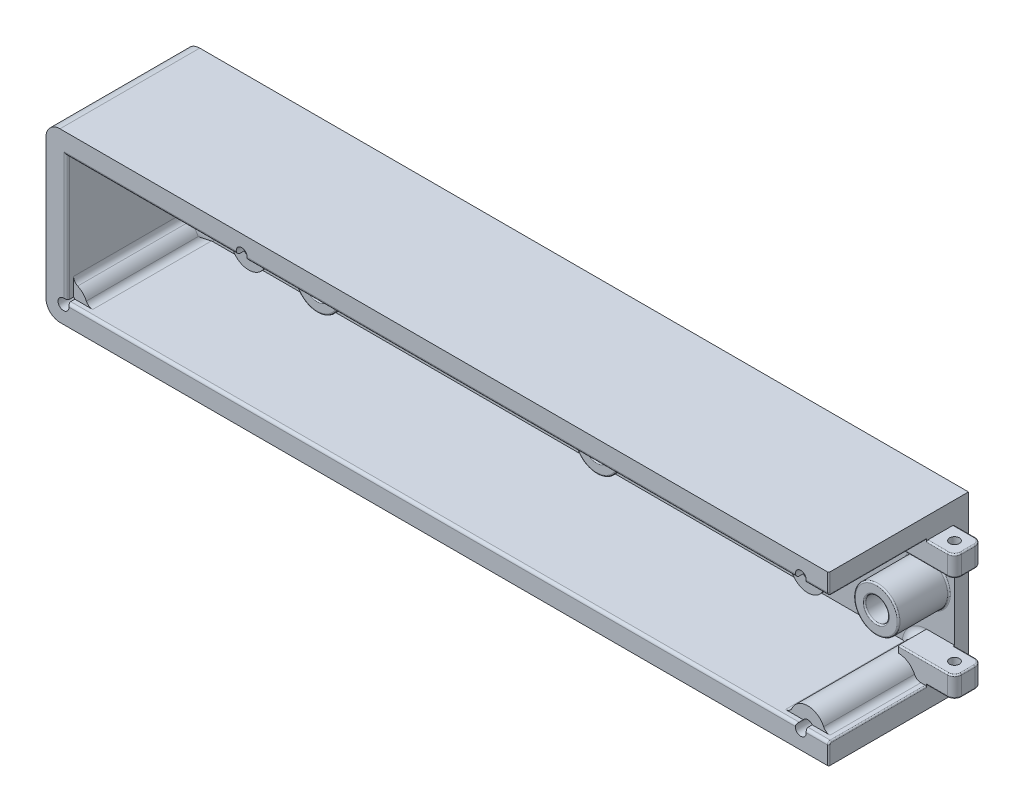
SolidWorks part; units mm, degrees
ref_plane "Front Plane" through (0, 0, 0) normal (0, 0, 1) x (1, 0, 0)
ref_plane "Top Plane" through (0, 0, 0) normal (0, 1, 0) x (1, 0, 0)
ref_plane "Right Plane" through (0, 0, 0) normal (1, 0, 0) x (0, 0, -1)
sketch "Sketch1" plane through (0, 0, 0) normal (0, 0, 1) x (1, 0, 0)
  line L0 (-50, 0) -> (0, 0) construction
  line L1 (-420, -70) -> (420, -70)
  line L2 (-420, -70) -> (-420, 70)
  line L3 (-420, 70) -> (420, 70)
  line L4 (420, -70) -> (420, 70)
  line L5 (-420, -70) -> (420, 70) construction
  line L6 (-420, 70) -> (420, -70) construction
  line L7 (0, 0) -> (50, 0) construction
  line L8 (250, 0) -> (350, 0) construction
  line L9 (333.7, -57.5) -> (333.7, 17.5)
  line L14 (334, -40) -> (350, 0) construction
  line L15 (334, 40) -> (334.4358, 38.9104) construction
  line L16 (336.5, 20.3) -> (363.5, 20.3)
  line L17 (366.3, -57.5) -> (366.3, 17.5)
  line L18 (336.5, -60.3) -> (363.5, -60.3)
  line L21 (365.5642, -38.9104) -> (366, -40) construction
  line L22 (365.5642, 38.9104) -> (366, 40) construction
  circle A0 centre (-350, 0) radius 4.15
  circle A1 centre (-250, 0) radius 4.15
  circle A2 centre (-150, 0) radius 4.15
  circle A3 centre (-50, 0) radius 4.15
  circle A4 centre (50, 0) radius 4.15
  circle A5 centre (150, 0) radius 4.15
  circle A6 centre (250, 0) radius 4.15
  circle A8 centre (350, 0) radius 4.15 [skipped]
  arc A13 (333.7, 17.5) -> (336.5, 20.3) centre (336.5, 17.5) cw
  arc A14 (363.5, 20.3) -> (366.3, 17.5) centre (363.5, 17.5) cw
  arc A15 (363.5, -60.3) -> (366.3, -57.5) centre (363.5, -57.5) ccw
  arc A16 (336.5, -60.3) -> (333.7, -57.5) centre (336.5, -57.5) cw
  point P0 (0, 0)
  dimension "D3" = 8.3
  dimension "D5" = 80
  dimension "D1" = 840
  dimension "D2" = 140
  dimension "D6" = 32
  dimension "D4" = 8
extrude "Boss-Extrude1" add sketch "Sketch1" along normal blind 5
sketch "Sketch2" plane through (0, 0, 5) normal (0, 0, 1) x (1, 0, 0)
  circle A0 centre (-350, 0) radius 8
  circle A1 centre (-350, 0) radius 4.15
extrude "Boss-Extrude3" add sketch "Sketch2" along normal blind 18
pattern_linear "LPattern1" count 7 spacing 100 along (1, 0, 0) of "Boss-Extrude3"
sketch "Sketch4" plane through (0, 0, 0) normal (0, 0, -1) x (-1, 0, 0)
  line L1 (-372.738, 24.1165) -> (-327.1271, 24.1165)
  line L2 (-372.738, 24.1165) -> (-372.738, -63.8212)
  line L3 (-372.738, -63.8212) -> (-327.1271, -63.8212)
  line L4 (-327.1271, 24.1165) -> (-327.1271, -63.8212)
extrude "Boss-Extrude4" add sketch "Sketch4" against normal blind 1
sketch "Sketch5" plane through (0, 70, 0) normal (0, 1, 0) x (1, 0, 0)
  line L4 (420, 0) -> (-420, 0)
  line L5 (-420, 0) -> (-420, -5)
  line L6 (-420, -5) -> (420, -5)
  line L7 (420, -5) -> (420, 0)
  line L8 (420, 0) -> (-420, 0)
  line L9 (-420, 0) -> (-420, -5)
  line L10 (-420, -5) -> (420, -5)
  line L11 (420, -5) -> (420, 0)
  dimension "D1" = 0
extrude "Cut-Extrude1" cut sketch "Sketch5" against normal blind 40
sketch "Sketch6" plane through (0, 0, 5) normal (0, 0, 1) x (1, 0, 0)
  line L0 (420, -70) -> (420, 30) construction
  line L1 (-420, -70) -> (300, -70)
  line L2 (-420, -70) -> (-420, -30)
  line L3 (-420, -30) -> (300, -30)
  line L4 (300, -70) -> (300, -30)
  dimension "D1" = 40
  dimension "D2" = 120
extrude "Cut-Extrude2" cut sketch "Sketch6" against normal through all
fillet "Fillet1" radius 5 4 edges at (300, -70, 2.5) (300, -30, 2.5) (-420, -30, 2.5) (-420, 30, 2.5)
fillet "Fillet2" radius 0.5 29 edges at (365.4799, -59.4799, 5) (350, -60.3, 5) (334.5201, -59.4799, 5) (333.7, -20, 5) (334.5201, 19.4799, 5) (350, 20.3, 5) (365.4799, 19.4799, 5) (-145.85, 0, 23) (-142, 0, 23) (-245.85, 0, 23) (-242, 0, 23) (366.3, -20, 5) (254.15, 0, 23) (258, 0, 23) (154.15, 0, 23) (158, 0, 23) (54.15, 0, 23) (58, 0, 23) (-45.85, 0, 23) (-42, 0, 23) (242, 0, 5) (142, 0, 5) (42, 0, 5) (-58, 0, 5) (-158, 0, 5) (-258, 0, 5) (-345.85, 0, 23) (-342, 0, 23) (-358, 0, 5)
fillet "Fillet3" radius 1 8 edges at (334.5201, 19.4799, 1) (333.7, -20, 1) (334.5201, -59.4799, 1) (350, -60.3, 1) (365.4799, -59.4799, 1) (366.3, -20, 1) (365.4799, 19.4799, 1) (350, 20.3, 1)
sketch "Sketch8" plane through (0, 0, 5) normal (0, 0, 1) x (1, 0, 0)
  line L0 (412.625, -62.625) -> (412.625, 22.625)
  line L1 (412.625, 22.625) -> (-412.625, 22.625)
  line L2 (-412.625, 22.625) -> (-412.625, -22.625)
  line L3 (-412.625, -22.625) -> (295, -22.625)
  line L4 (307.375, -35) -> (307.375, -62.625)
  line L5 (307.375, -62.625) -> (412.625, -62.625)
  line L6 (300, -35) -> (300, -65)
  line L7 (305, -70) -> (420, -70)
  line L8 (420, -70) -> (420, 30)
  line L9 (420, 30) -> (-415, 30)
  line L10 (-420, 25) -> (-420, -25)
  line L11 (-415, -30) -> (295, -30)
  line L12 (300, -35) -> (300, -65)
  line L13 (305, -70) -> (420, -70)
  line L14 (420, -70) -> (420, 30)
  line L15 (420, 30) -> (-415, 30)
  line L16 (-420, 25) -> (-420, -25)
  line L17 (-415, -30) -> (295, -30)
  arc A0 (-412.625, 22.625) -> (-412.625, 22.625) centre (-412.625, 22.625) ccw
  arc A1 (-412.625, -22.625) -> (-412.625, -22.625) centre (-412.625, -22.625) ccw
  arc A2 (307.375, -35) -> (295, -22.625) centre (295, -35) ccw
  arc A3 (307.375, -62.625) -> (307.375, -62.625) centre (307.375, -62.625) ccw
  arc A4 (300, -65) -> (305, -70) centre (305, -65) ccw
  arc A5 (-415, 30) -> (-420, 25) centre (-415, 25) ccw
  arc A6 (-420, -25) -> (-415, -30) centre (-415, -25) ccw
  arc A7 (300, -35) -> (295, -30) centre (295, -35) ccw
  arc A8 (300, -65) -> (305, -70) centre (305, -65) ccw
  arc A9 (-415, 30) -> (-420, 25) centre (-415, 25) ccw
  arc A10 (-420, -25) -> (-415, -30) centre (-415, -25) ccw
  arc A11 (300, -35) -> (295, -30) centre (295, -35) ccw
  dimension "D1" = 0
  dimension "D2" = 7.375
extrude "Boss-Extrude5" add sketch "Sketch8" along normal blind 45
ref_plane "Plane1" through (-140, 0, 0) normal (-1, 0, 0) x (0, 0, 1)
ref_plane "Plane2" through (140, 0, 0) normal (-1, 0, 0) x (0, 0, 1)
fillet "Fillet4" radius 1 3 edges at (307.375, -48.8125, 50) (303.7504, -26.2496, 50) (-58.8125, -22.625, 50)
sketch "Sketch10" plane through (0, 0, 50) normal (0, 0, 1) x (1, 0, 0)
  line L0 (412.625, -62.625) -> (412.625, 22.625) construction
  line L1 (412.625, 22.625) -> (420, 22.625)
  line L2 (412.625, 22.625) -> (412.625, -62.625)
  line L3 (412.625, -62.625) -> (420, -62.625)
  line L4 (420, 22.625) -> (420, -62.625)
  line L5 (412.625, -62.625) -> (412.625, 22.625) construction
  line L6 (420, -70) -> (420, 30) construction
extrude "Cut-Extrude3" cut sketch "Sketch10" against normal up to surface (45 mm away) up to face at (130.3304, -22.5267, 5)
fillet "Fillet5" radius 1 3 edges at (-412.625, -0.5, 50) (3.6875, 22.625, 50) (363.1875, -62.625, 50)
sketch "Sketch11" plane through (0, 0, 0) normal (0, 0, -1) x (-1, 0, 0)
  circle A0 centre (-250, 0) radius 4.15
  circle A1 centre (-150, 0) radius 4.15
  circle A2 centre (-50, 0) radius 4.15
  circle A3 centre (50, 0) radius 4.15
  circle A4 centre (150, 0) radius 4.15
  circle A5 centre (250, 0) radius 4.15
  circle A6 centre (350, 0) radius 4.15
  dimension "D1" = 7
extrude "Boss-Extrude6" add sketch "Sketch11" against normal blind 5
mirror "Mirror1" about plane through (420, -70, 5) normal (-1, 0, 0) of bodies 110
delete or keep bodies "Body-Delete/Keep 2" type delete bodies bodies 110
sketch "Sketch12" plane through (420, 0, 0) normal (-1, 0, 0) x (0, 0, 1)
  line L8 (50, 23.625) -> (50, 30)
  line L9 (50, 30) -> (0, 30)
  line L10 (0, 30) -> (0, -70)
  line L11 (0, -70) -> (50, -70)
  line L12 (50, -70) -> (50, -63.625)
  line L13 (49, -62.625) -> (5, -62.625)
  line L14 (5, -62.625) -> (5, 22.625)
  line L15 (5, 22.625) -> (49, 22.625)
  line L16 (50, 23.625) -> (50, 30)
  line L17 (50, 30) -> (0, 30)
  line L18 (0, 30) -> (0, -70)
  line L19 (0, -70) -> (50, -70)
  line L20 (50, -70) -> (50, -63.625)
  line L21 (49, -62.625) -> (5, -62.625)
  line L22 (5, -62.625) -> (5, 22.625)
  line L23 (5, 22.625) -> (49, 22.625)
  arc A2 (50, -63.625) -> (49, -62.625) centre (49, -63.625) ccw
  arc A3 (49, 22.625) -> (50, 23.625) centre (49, 23.625) ccw
  arc A4 (50, -63.625) -> (49, -62.625) centre (49, -63.625) ccw
  arc A5 (49, 22.625) -> (50, 23.625) centre (49, 23.625) ccw
  dimension "D1" = 0
extrude "Cut-Extrude4" cut sketch "Sketch12" against normal blind 20
sketch "Sketch13" plane through (0, -70, 0) normal (0, -1, 0) x (1, 0, 0)
  line L0 (535, 50) -> (440, 50) construction
  line L1 (455, 35) -> (467, 35)
  line L2 (455, 35) -> (455, 23)
  line L3 (455, 23) -> (467, 23)
  line L4 (467, 35) -> (467, 23)
  line L5 (440, 0) -> (440, 50) construction
  point P6 (455, 29)
  dimension "D1" = 12
  dimension "D2" = 12
  dimension "D3" = 15
  dimension "D4" = 15
extrude "Cut-Extrude5" cut sketch "Sketch13" against normal blind 5
sketch "Sketch14" plane through (0, -70, 0) normal (0, -1, 0) x (1, 0, 0)
  line L0 (467, 35) -> (455, 35) construction
  line L1 (456.5, 37) -> (465.5, 37)
  line L2 (456.5, 37) -> (456.5, 21)
  line L3 (456.5, 21) -> (465.5, 21)
  line L4 (465.5, 37) -> (465.5, 21)
  line L5 (455, 35) -> (455, 23) construction
  point P4 (461, 35)
  point P5 (455, 29)
  point P8 (461, 37)
  point P11 (456.5, 29)
  dimension "D1" = 9
  dimension "D2" = 16
extrude "Cut-Extrude6" cut sketch "Sketch14" against normal up to next
sketch "Sketch20" plane through (0, 0, 50) normal (0, 0, 1) x (1, 0, 0)
  line L0 (440, 30) -> (1255, 30) construction
  line L1 (1255, -30) -> (545, -30) construction
  line L2 (540, -35) -> (540, -65) construction
  line L3 (535, -70) -> (440, -70) construction
  line L5 (440, 23.625) -> (440, 30) construction
  line L12 (1255, 30) -> (440, 30)
  line L13 (440, 30) -> (440, 23.625)
  line L14 (440, 23.625) -> (1253.625, 23.625)
  line L15 (1253.625, 23.625) -> (1253.625, -23.625)
  line L16 (1253.625, -23.625) -> (545, -23.625)
  line L17 (533.625, -35) -> (533.625, -63.625)
  line L18 (533.625, -63.625) -> (440, -63.625)
  line L19 (440, -63.625) -> (440, -70)
  line L20 (440, -70) -> (535, -70)
  line L21 (540, -65) -> (540, -35)
  line L22 (545, -30) -> (1255, -30)
  line L23 (1260, -25) -> (1260, 25)
  line L35 (1260, -25) -> (1260, 25)
  circle A0 centre (790, 23.75) radius 1.95
  circle A1 centre (790, -23.75) radius 1.95
  circle A4 centre (460, 23.75) radius 1.95
  arc A5 (545, -23.625) -> (533.625, -35) centre (545, -35) ccw
  arc A6 (535, -70) -> (540, -65) centre (535, -65) ccw
  arc A7 (545, -30) -> (540, -35) centre (545, -35) ccw
  arc A8 (1255, -30) -> (1260, -25) centre (1255, -25) ccw
  arc A9 (1260, 25) -> (1255, 30) centre (1255, 25) ccw
  arc A11 (535, -70) -> (540, -65) centre (535, -65) ccw
  arc A12 (545, -30) -> (540, -35) centre (545, -35) ccw
  arc A13 (1255, -30) -> (1260, -25) centre (1255, -25) ccw
  arc A14 (1260, 25) -> (1255, 30) centre (1255, 25) ccw
  circle A15 centre (533.75, -63.75) radius 1.95
  circle A16 centre (690, 23.75) radius 1.95
  circle A17 centre (890, -23.75) radius 1.95
  circle A18 centre (990, 23.75) radius 1.95
  circle A19 centre (690, -23.75) radius 1.95
  circle A20 centre (890, 23.75) radius 1.95
  circle A21 centre (990, -23.75) radius 1.95
  circle A22 centre (1190, 23.75) radius 1.95
  circle A23 centre (1253.75, -23.75) radius 1.95
  point P13 (890, 0)
  point P28 (790, 0)
  point P44 (690, 0)
  point P46 (689.7552, 26.25)
  point P49 (990, 0)
  point P63 (1190, 0)
  dimension "D3" = 20
  dimension "D4" = 3.9
  dimension "D5" = 6.25
  dimension "D2" = 6.25
  dimension "D6" = 6.25
  dimension "D7" = 6.25
  dimension "D8" = 6.25
  dimension "D9" = 6.25
  dimension "D10" = 6.25
  dimension "D11" = 6.25
  dimension "D1" = 0
extrude "Cut-Extrude8" cut sketch "Sketch20" against normal blind 26 contours A4 | A15 | A16 | A19 | A20 | A17 | A18 | A21 | A22 | A23 | A1 | A0
ref_plane "Plane5" through (700, 0, 0) normal (-1, 0, 0) x (0, 0, 1)
ref_plane "Plane6" through (980, 0, 0) normal (-1, 0, 0) x (0, 0, 1)
ref_plane "Plane7" through (0, 0, 47.5) normal (0, 0, 1) x (1, 0, 0)
sketch "Sketch22" plane through (0, 0, 47.5) normal (0, 0, 1) x (1, 0, 0)
  circle A0 centre (460, 23.75) radius 1.95
  circle A1 centre (460, 23.75) radius 6.25
  circle A2 centre (690, 23.75) radius 1.95
  circle A3 centre (690, 23.75) radius 6.25
  circle A4 centre (790, 23.75) radius 1.95
  circle A5 centre (790, 23.75) radius 6.25
  circle A6 centre (890, 23.75) radius 1.95
  circle A7 centre (890, 23.75) radius 6.25
  circle A8 centre (990, 23.75) radius 1.95
  circle A9 centre (990, 23.75) radius 6.25
  circle A10 centre (1190, 23.75) radius 1.95
  circle A11 centre (1190, 23.75) radius 6.25
  circle A12 centre (1253.75, -23.75) radius 1.95
  circle A13 centre (1253.75, -23.75) radius 6.25
  circle A14 centre (990, -23.75) radius 1.95
  circle A16 centre (990, -23.75) radius 6.25
  circle A17 centre (890, -23.75) radius 1.95
  circle A18 centre (890, -23.75) radius 6.25
  circle A19 centre (790, -23.75) radius 1.95
  circle A20 centre (790, -23.75) radius 6.25
  circle A21 centre (690, -23.75) radius 1.95
  circle A22 centre (690, -23.75) radius 6.25
  circle A23 centre (533.75, -63.75) radius 1.95
  circle A24 centre (533.75, -63.75) radius 6.25
extrude "Boss-Extrude8" add sketch "Sketch22" against normal up to surface (42.5 mm away) up to face at (1198.5, 0, 5)
sketch "Sketch23" plane through (0, 0, 5) normal (0, 0, 1) x (1, 0, 0)
  line L1 (461.5928, 22.625) -> (458.4072, 22.625)
  line L2 (461.5928, 22.625) -> (458.4072, 22.625)
  line L3 (691.5928, 22.625) -> (688.4072, 22.625)
  line L4 (691.5928, 22.625) -> (688.4072, 22.625)
  line L5 (791.5928, 22.625) -> (788.4072, 22.625)
  line L6 (791.5928, 22.625) -> (788.4072, 22.625)
  line L7 (891.5928, 22.625) -> (888.4072, 22.625)
  line L8 (891.5928, 22.625) -> (888.4072, 22.625)
  line L9 (991.5928, 22.625) -> (988.4072, 22.625)
  line L10 (991.5928, 22.625) -> (988.4072, 22.625)
  line L11 (1191.5928, 22.625) -> (1188.4072, 22.625)
  line L12 (1191.5928, 22.625) -> (1188.4072, 22.625)
  line L13 (988.4072, -22.625) -> (991.5928, -22.625)
  line L14 (1252.1572, -22.625) -> (1252.625, -22.625)
  line L15 (1252.625, -22.625) -> (1252.625, -22.1572)
  line L16 (1252.1572, -22.625) -> (1252.625, -22.625)
  line L17 (1252.625, -22.625) -> (1252.625, -22.1572)
  line L18 (988.4072, -22.625) -> (991.5928, -22.625)
  line L19 (888.4072, -22.625) -> (891.5928, -22.625)
  line L20 (888.4072, -22.625) -> (891.5928, -22.625)
  line L21 (788.4072, -22.625) -> (791.5928, -22.625)
  line L22 (788.4072, -22.625) -> (791.5928, -22.625)
  line L23 (688.4072, -22.625) -> (691.5928, -22.625)
  line L24 (688.4072, -22.625) -> (691.5928, -22.625)
  line L26 (532.1572, -62.625) -> (532.625, -62.625)
  line L27 (532.625, -62.625) -> (532.625, -62.1572)
  line L28 (532.1572, -62.625) -> (532.625, -62.625)
  line L29 (532.625, -62.625) -> (532.625, -62.1572)
  arc A1 (458.4072, 22.625) -> (461.5928, 22.625) centre (460, 23.75) ccw
  arc A2 (458.4072, 22.625) -> (461.5928, 22.625) centre (460, 23.75) ccw
  arc A3 (688.4072, 22.625) -> (691.5928, 22.625) centre (690, 23.75) ccw
  arc A4 (688.4072, 22.625) -> (691.5928, 22.625) centre (690, 23.75) ccw
  arc A5 (788.4072, 22.625) -> (791.5928, 22.625) centre (790, 23.75) ccw
  arc A6 (788.4072, 22.625) -> (791.5928, 22.625) centre (790, 23.75) ccw
  arc A7 (888.4072, 22.625) -> (891.5928, 22.625) centre (890, 23.75) ccw
  arc A8 (888.4072, 22.625) -> (891.5928, 22.625) centre (890, 23.75) ccw
  arc A9 (988.4072, 22.625) -> (991.5928, 22.625) centre (990, 23.75) ccw
  arc A10 (988.4072, 22.625) -> (991.5928, 22.625) centre (990, 23.75) ccw
  arc A11 (1188.4072, 22.625) -> (1191.5928, 22.625) centre (1190, 23.75) ccw
  arc A12 (1188.4072, 22.625) -> (1191.5928, 22.625) centre (1190, 23.75) ccw
  arc A13 (1252.625, -22.1572) -> (1252.1572, -22.625) centre (1253.75, -23.75) ccw
  arc A14 (1252.625, -22.1572) -> (1252.1572, -22.625) centre (1253.75, -23.75) ccw
  arc A15 (991.5928, -22.625) -> (988.4072, -22.625) centre (990, -23.75) ccw
  arc A16 (991.5928, -22.625) -> (988.4072, -22.625) centre (990, -23.75) ccw
  arc A17 (891.5928, -22.625) -> (888.4072, -22.625) centre (890, -23.75) ccw
  arc A18 (891.5928, -22.625) -> (888.4072, -22.625) centre (890, -23.75) ccw
  arc A19 (791.5928, -22.625) -> (788.4072, -22.625) centre (790, -23.75) ccw
  arc A20 (791.5928, -22.625) -> (788.4072, -22.625) centre (790, -23.75) ccw
  arc A21 (691.5928, -22.625) -> (688.4072, -22.625) centre (690, -23.75) ccw
  arc A22 (691.5928, -22.625) -> (688.4072, -22.625) centre (690, -23.75) ccw
  arc A23 (532.625, -62.1572) -> (532.1572, -62.625) centre (533.75, -63.75) ccw
  arc A24 (532.625, -62.1572) -> (532.1572, -62.625) centre (533.75, -63.75) ccw
  dimension "D1" = 0
  dimension "D2" = 0
  dimension "D3" = 0
  dimension "D4" = 0
  dimension "D5" = 0
  dimension "D6" = 0
  dimension "D7" = 0
  dimension "D8" = 0
  dimension "D9" = 0
  dimension "D10" = 0
  dimension "D11" = 0
  dimension "D12" = 0
extrude "Boss-Extrude9" add sketch "Sketch23" along normal up to surface (19 mm away) up to face at (460, 24.1625, 24)
fillet "Fillet6" radius 2.5 36 edges at (1252.625, -17.6021, 26.25) (1247.6021, -22.625, 26.25) (1249.3306, -19.3306, 5) (996.1479, -22.625, 26.25) (990, -17.5, 5) (983.8521, -22.625, 26.25) (890, -17.5, 5) (883.8521, -22.625, 26.25) (896.1479, -22.625, 26.25) (796.1479, -22.625, 26.25) (783.8521, -22.625, 26.25) (790, -17.5, 5) (696.1479, -22.625, 26.25) (690, -17.5, 5) (683.8521, -22.625, 26.25) (532.625, -57.6021, 26.25) (529.3306, -59.3306, 5) (527.6021, -62.625, 26.25) (453.8521, 22.625, 26.25) (466.1479, 22.625, 26.25) (683.8521, 22.625, 26.25) (696.1479, 22.625, 26.25) (783.8521, 22.625, 26.25) (796.1479, 22.625, 26.25) (896.1479, 22.625, 26.25) (883.8521, 22.625, 26.25) (983.8521, 22.625, 26.25) (996.1479, 22.625, 26.25) (1196.1479, 22.625, 26.25) (1183.8521, 22.625, 26.25) (1190, 17.5, 5) (990, 17.5, 5) (890, 17.5, 5) (790, 17.5, 5) (690, 17.5, 5) (460, 17.5, 5)
ref_plane "Plane8" through (980, 0, 0) normal (-1, 0, 0) x (0, 0, 1)
sketch "Sketch25" plane through (440, 0, 0) normal (-1, 0, 0) x (0, 0, 1)
  line L1 (-34.7781, 41.231) -> (83.3252, 41.231)
  line L2 (-34.7781, 41.231) -> (-34.7781, -92.647)
  line L3 (-34.7781, -92.647) -> (83.3252, -92.647)
  line L4 (83.3252, 41.231) -> (83.3252, -92.647)
extrude "Cut-Extrude10" cut sketch "Sketch25" against normal up to surface (540 mm away) up to plane "Plane8"
sketch "Sketch26" plane through (0, 0, 5) normal (0, 0, 1) x (1, 0, 0)
  line L0 (990, 15) -> (980, 15)
  line L1 (980, -22.625) -> (980, 22.625) construction
  line L2 (980, 15) -> (980, 22.625)
  line L3 (980, 22.625) -> (981.3226, 22.625) construction
  line L4 (980, 22.625) -> (988.4072, 22.625)
  line L5 (990, 21.8) -> (990, 15)
  circle A0 centre (990, 23.75) radius 1.95 construction
  arc A1 (988.4072, 22.625) -> (990, 21.8) centre (990, 23.75) ccw
  arc A2 (981.3226, 22.625) -> (998.6774, 22.625) centre (990, 23.75) ccw construction
  dimension "D1" = 0
extrude "Boss-Extrude10" add sketch "Sketch26" along normal blind 10
sketch "Sketch27" plane through (980, 0, 0) normal (-1, 0, 0) x (0, 0, 1)
  line L0 (5, 22.625) -> (5, -15.0726) construction
  line L1 (15, 15) -> (5.125, 15)
  line L2 (15, 15) -> (15, 22.41)
  line L3 (15, 22.41) -> (5.125, 22.41)
  line L4 (5.125, 15) -> (5.125, 22.41)
  line L5 (15, 22.625) -> (47.5, 22.625) construction
  dimension "D1" = 0.125
  dimension "D2" = 0.215
extrude "Boss-Extrude11" add sketch "Sketch27" along normal blind 10
fillet "Fillet7" radius 2.5 2 edges at (970, 18.705, 5.125) (970, 18.705, 15)
fillet "Fillet8" radius 0.5 13 edges at (980, 22.625, 32) (980, 22.9179, 49.7071) (976.25, 22.41, 15) (970.7322, 22.41, 14.2678) (976.25, 22.41, 5.125) (970.7322, 22.41, 5.8572) (976.25, 15, 5.125) (970.7322, 15, 5.8572) (981.25, 15, 15) (970.7322, 15, 14.2678) (980, 26.8125, 50) (970, 22.41, 10.0625) (970, 15, 10.0625)
mirror "Mirror2" about plane through (0, 0, 0) normal (0, 1, 0) of "Fillet8", "Fillet7", "Boss-Extrude11", "Boss-Extrude10"
sketch "Sketch28" plane through (0, -22.41, 0) normal (0, -1, 0) x (1, 0, 0)
  line L0 (970, 7.625) -> (970, 12.5) construction
  circle A0 centre (975, 10) radius 1.75
  dimension "D1" = 5
  dimension "D2" = 5
extrude "Cut-Extrude11" cut sketch "Sketch28" against normal through all
mirror "Mirror3" about plane through (1260, -70, 5) normal (-1, 0, 0) of bodies 125
delete or keep bodies "Body-Delete/Keep 3" type delete bodies bodies 125
